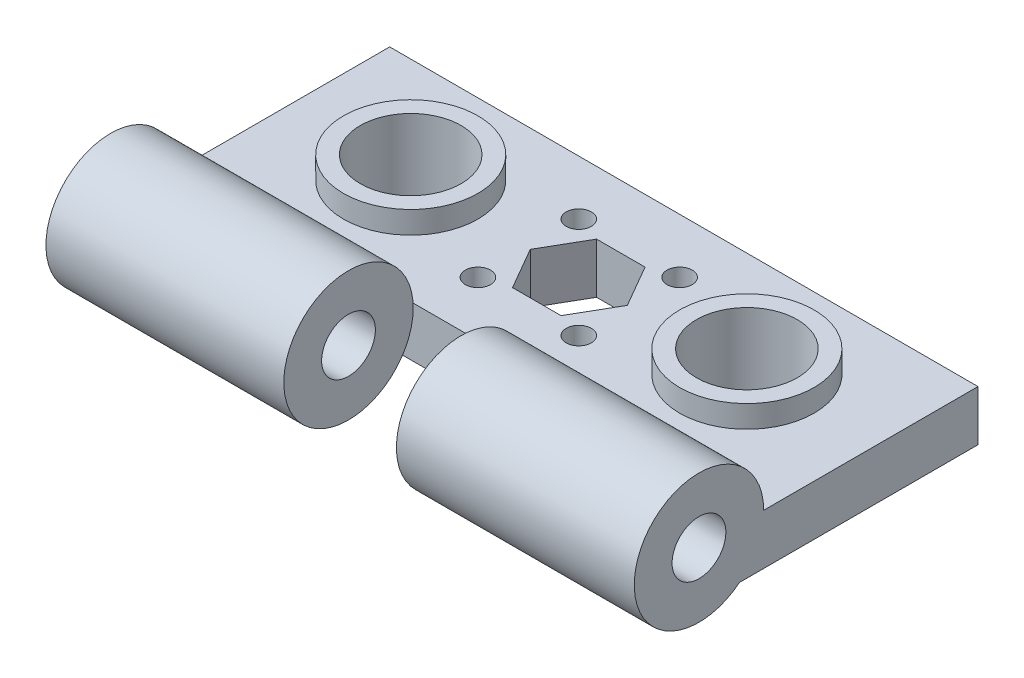
SolidWorks part; units mm, degrees
ref_plane "Front Plane" through (0, 0, 0) normal (0, 0, 1) x (1, 0, 0)
ref_plane "Top Plane" through (0, 0, 0) normal (0, 1, 0) x (1, 0, 0)
ref_plane "Right Plane" through (0, 0, 0) normal (1, 0, 0) x (0, 0, -1)
sketch "Sketch1" plane through (0, 0, 0) normal (0, 1, 0) x (1, 0, 0)
  line L0 (0, 30) -> (70, 30) construction
  line L1 (0, 0) -> (70, 0) construction
  line L2 (0, 0) -> (0, 30) construction
  line L3 (0, 30) -> (70, 30) construction
  line L4 (70, 0) -> (70, 30) construction
  line L5 (35, 30) -> (35, 0) construction
  line L6 (70, 0) -> (60, 0)
  line L7 (60, 0) -> (60, 5)
  line L8 (60, 5) -> (10, 5)
  line L9 (10, 0) -> (10, 5)
  line L10 (0, 0) -> (10, 0)
  line L11 (0, 0) -> (0, 30)
  line L12 (0, 30) -> (70, 30)
  line L13 (70, 30) -> (70, 0)
  line L14 (30.6699, 15) -> (39.3301, 20) construction
  line L15 (40.7735, 17.5) -> (37.8868, 22.5)
  line L16 (37.8868, 22.5) -> (32.1132, 22.5)
  line L17 (32.1132, 22.5) -> (29.2265, 17.5)
  line L18 (29.2265, 17.5) -> (32.1132, 12.5)
  line L19 (32.1132, 12.5) -> (37.8868, 12.5)
  line L20 (37.8868, 12.5) -> (40.7735, 17.5)
  line L21 (35, 5) -> (35, 30) construction
  line L22 (35, 17.5) -> (15, 17.5) construction
  line L24 (29, 23.5) -> (41, 23.5) construction
  line L25 (29, 23.5) -> (29, 11.5) construction
  line L26 (29, 11.5) -> (41, 11.5) construction
  line L27 (41, 23.5) -> (41, 11.5) construction
  line L28 (29, 23.5) -> (41, 11.5) construction
  line L29 (29, 11.5) -> (41, 23.5) construction
  circle A1 centre (35, 17.5) radius 5 construction
  circle A2 centre (15, 17.5) radius 6
  circle A3 centre (55, 17.5) radius 6
  circle A4 centre (41, 23.5) radius 1.5
  circle A5 centre (29, 23.5) radius 1.5
  circle A6 centre (29, 11.5) radius 1.5
  circle A7 centre (41, 11.5) radius 1.5
  point P11 (35, 5)
  point P25 (35, 17.5)
  dimension "D5" = 12
  dimension "D8" = 3
  dimension "D1" = 70
  dimension "D2" = 30
  dimension "D3" = 5
  dimension "D4" = 10
  dimension "D6" = 20
  dimension "D7" = 12
extrude "Boss-Extrude1" add sketch "Sketch1" along normal blind 6
ref_plane "Plane1" through (0, 3, 0) normal (0, 1, 0) x (1, 0, 0)
sketch "Sketch2" plane through (0, 3, 0) normal (0, 1, 0) x (1, 0, 0)
  circle A1 centre (15, 17.5) radius 6
  circle A2 centre (15, 17.5) radius 8
  circle A3 centre (15, 17.5) radius 8
  circle A4 centre (15, 17.5) radius 6 construction
  circle A6 centre (55, 17.5) radius 6
  circle A7 centre (55, 17.5) radius 8
  circle A8 centre (55, 17.5) radius 8
  dimension "D1" = 2
  dimension "D2" = 2
extrude "Boss-Extrude2" add sketch "Sketch2" along normal blind 5.65 and the other way blind 5.65
sketch "Sketch3" plane through (10, 0, 0) normal (1, 0, 0) x (0, 0, -1)
  line L0 (0, 6) -> (5, 6) construction
  line L1 (5, 6) -> (5, 0) construction
  circle A2 centre (-3.2, 6) radius 3.2
  circle A3 centre (-3.2, 6) radius 7.7
  point P3 (0, 0)
  dimension "D1" = 4.5
  dimension "D2" = 6.4
  dimension "D3" = 8.2
extrude "Boss-Extrude9" add sketch "Sketch3" along normal up to surface and the other way up to surface up to face at (70, 3, -15) other way up to face at (0, 3, -15)
ref_plane "Plane3" through (35, 0, 0) normal (1, 0, 0) x (0, 0, -1)
sketch "Sketch4" plane through (35, 0, 0) normal (1, 0, 0) x (0, 0, -1)
  circle A0 centre (-3.2, 6) radius 7.7
  arc A1 (4.5, 6) -> (1.626, 0) centre (-3.2, 6) ccw construction
extrude "Cut-Extrude1" cut sketch "Sketch4" against normal blind 6.7 and the other way blind 6.7
